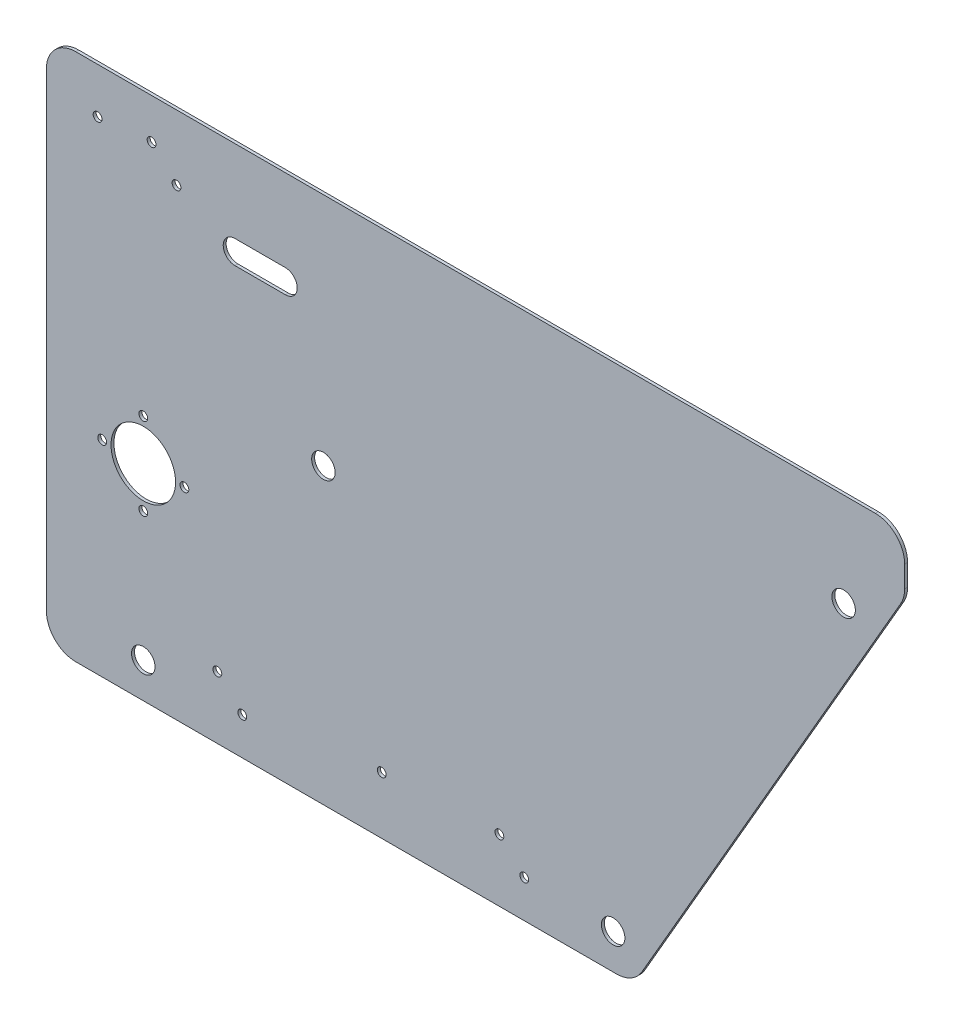
SolidWorks part; units mm, degrees
ref_plane "Front Plane" through (0, 0, 0) normal (0, 0, 1) x (1, 0, 0)
ref_plane "Top Plane" through (0, 0, 0) normal (0, 1, 0) x (1, 0, 0)
ref_plane "Right Plane" through (0, 0, 0) normal (1, 0, 0) x (0, 0, -1)
sketch "Sketch1" plane through (0, 0, 0) normal (0, 0, 1) x (1, 0, 0)
  line L0 (100, 80) -> (192.376, 80)
  line L1 (-100, -80) -> (100, -80)
  line L2 (-100, -80) -> (-100, 80)
  line L3 (-100, 80) -> (100, 80)
  line L4 (100, -80) -> (100, 80)
  line L5 (-100, -80) -> (100, 80) construction
  line L6 (-100, 80) -> (100, -80) construction
  line L7 (192.376, 80) -> (100, -80)
  line L8 (100, 80) -> (100, -80)
  line L10 (-100, 80) -> (192.376, 80)
  line L11 (-100, 80) -> (-100, 100)
  line L12 (-100, 100) -> (192.376, 100)
  line L13 (192.376, 80) -> (192.376, 100)
  point P0 (0, 0)
  dimension "D1" = 160
  dimension "D2" = 200
  dimension "D3" = 30
  dimension "D4" = 20
extrude "Boss-Extrude1" add sketch "Sketch1" along normal blind 1 contours L1 L4 L3 L2 | L7 L0 L4 | L11 L10 L13 L12 region at (0, 0, 0) region at (130.792, 26.6667, 0)
fillet "Fillet1" radius 10 5 edges at (100, -80, 0.5) (-100, -80, 0.5) (192.376, 100, 0.5) (-100, 100, 0.5) (192.376, 80, 0.5)
sketch "Sketch2" plane through (0, 0, 1) normal (0, 0, 1) x (1, 0, 0)
  line L0 (-90, -80) -> (94.2265, -80) construction
  line L1 (191.0363, 77.6795) -> (102.8868, -75) construction
  line L3 (-90, 100) -> (182.376, 100) construction
  line L4 (-35.7696, 68) -> (-18.5533, 68) construction
  line L7 (-100, -70) -> (-100, 90) construction
  line L9 (-35.7696, 72) -> (-18.5533, 72)
  line L10 (-35.7696, 64) -> (-18.5533, 64)
  circle A0 centre (93.0718, -68) radius 4
  circle A1 centre (171.5914, 68) radius 4
  circle A2 centre (-67, -10) radius 11
  circle A3 centre (-67, -68) radius 4
  circle A4 centre (-53, -10) radius 1.5
  circle A5 centre (-67, 4) radius 1.5
  circle A6 centre (-81, -10) radius 1.5
  circle A7 centre (-67, -24) radius 1.5
  circle A10 centre (-5.639, 20) radius 4
  arc A11 (-35.7696, 72) -> (-35.7696, 64) centre (-35.7696, 68) ccw
  arc A12 (-18.5533, 64) -> (-18.5533, 72) centre (-18.5533, 68) ccw
  circle A32 centre (62.7961, -67.2426) radius 1.5
  circle A33 centre (54.3108, -58.7574) radius 1.5
  circle A34 centre (-33.2742, -67.2426) radius 1.5
  circle A35 centre (-41.7595, -58.7574) radius 1.5
  circle A36 centre (14.2259, -60.5) radius 1.5
  circle A37 centre (-55.6882, 77.7574) radius 1.5
  circle A38 centre (-64.1735, 86.2426) radius 1.5
  circle A39 centre (-82.5763, 84.5) radius 1.5
  point P12 (-27.1615, 68)
  point P36 (0, 0)
  dimension "D3" = 8
  dimension "D4" = 8
  dimension "D9" = 22
  dimension "D10" = 8
  dimension "D12" = 3
  dimension "D13" = 3
  dimension "D14" = 3
  dimension "D15" = 3
  dimension "D16" = 14
  dimension "D20" = 4
  dimension "D22" = 8
  dimension "D23" = 3
  dimension "D1" = 12
  dimension "D2" = 12
  dimension "D5" = 32
  dimension "D6" = 12
  dimension "D7" = 33
  dimension "D8" = 70
  dimension "D11" = 12
  dimension "D17" = 14
  dimension "D18" = 14
  dimension "D19" = 14
  dimension "D21" = 80
extrude "Cut-Extrude1" cut sketch "Sketch2" against normal blind 3
